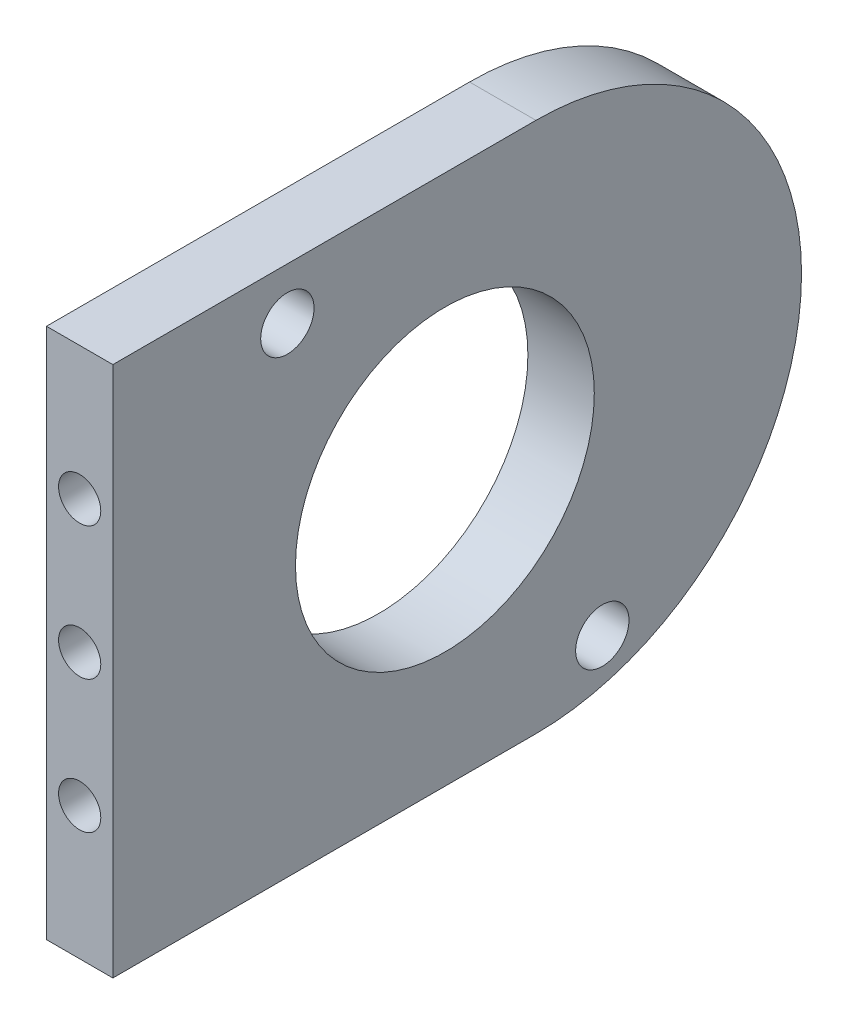
SolidWorks part; units mm, degrees
material "6061-T6 (SS)"
ref_plane "Front" through (0, 0, 0) normal (0, 0, 1) x (1, 0, 0)
ref_plane "Top" through (0, 0, 0) normal (0, 1, 0) x (1, 0, 0)
ref_plane "Right" through (0, 0, 0) normal (1, 0, 0) x (0, 0, -1)
sketch "Sketch2" plane through (0, 0, 0) normal (1, 0, 0) x (0, 0, -1)
  line L1 (-38.1, -25.4) -> (38.1, -25.4)
  line L2 (-38.1, -25.4) -> (-38.1, 25.4)
  line L3 (-38.1, 25.4) -> (38.1, 25.4)
  line L4 (38.1, -25.4) -> (38.1, 25.4)
  line L5 (-38.1, -25.4) -> (38.1, 25.4) construction
  line L6 (-38.1, 25.4) -> (38.1, -25.4) construction
  point P0 (0, 0)
  dimension "D1" = 76.2
  dimension "D2" = 50.8
extrude "Boss-Extrude2" add sketch "Sketch2" along normal blind 6.35
hole_wizard "#10-32 Tapped Hole1" positions "Sketch3" profile "Sketch5" tap size "#10-32" standard "ANSI Inch"
sketch "Sketch3" plane through (0, 0, 38.1) normal (0, 0, 1) x (1, 0, 0)
  line L0 (3.175, 25.4) -> (3.175, 12.7) construction
  line L1 (6.35, 25.4) -> (0, 25.4) construction
  line L3 (3.175, 12.7) -> (3.175, 0) construction
  line L4 (3.175, 0) -> (3.175, -12.7) construction
  line L5 (3.175, -12.7) -> (3.175, -25.4) construction
  line L6 (6.35, -25.4) -> (0, -25.4) construction
  point P0 (3.175, -12.7)
  point P2 (3.175, 0)
  point P6 (3.175, 12.7)
sketch "Sketch5" plane through (3.175, -12.7, 38.1) normal (1, 0, 0) x (0, -1, 0)
  line L0 (0, 0) -> (0, 13.2428)
  line L1 (0, 13.2428) -> (2.0193, 12.0294)
  line L2 (2.0193, 12.0294) -> (2.0193, 0)
  line L5 (2.0193, 0) -> (0, 0)
  line L10 (0, 13.2428) -> (-2.0193, 12.0294) construction
  line L11 (0, -6.35) -> (0, 107.95) construction
  dimension "Tap Drill Dia." = 4.0386
  dimension "Tap Drill Depth" = 12.0294
  dimension "Drill Angle" = 118
cosmetic thread "Hole Thread1" parameters "D1"=9.652, "D2"=4.826
cosmetic thread "Hole Thread3" parameters "D1"=9.652, "D2"=4.826
cosmetic thread "Hole Thread4" parameters "D1"=9.652, "D2"=4.826
sketch "Sketch6" plane through (6.35, 0, 0) normal (1, 0, 0) x (0, 0, -1)
  line L0 (-38.1, 25.4) -> (-38.1, -25.4) construction
  line L1 (-38.1, -25.4) -> (38.1, -25.4) construction
  circle A0 centre (-6.35, 0) radius 14.2875
  dimension "D1" = 31.75
  dimension "D3" = 28.575
  dimension "D2" = 25.4
extrude "Cut-Extrude1" cut sketch "Sketch6" against normal through all
sketch "Sketch10" plane through (0, 0, 0) normal (-1, 0, 0) x (0, 0, 1)
  point P3 (-8.7041, -20.4408)
  point P8 (21.4132, 20.4687)
hole_wizard "#10 Clearance Hole1" positions "Sketch10" profile "Sketch9" hole size "#10" standard "ANSI Inch"
sketch "Sketch9" plane through (0, -20.4408, -8.7041) normal (0, 1, 0) x (0, 0, 1)
  line L0 (0, 0) -> (0, 13.5633)
  line L1 (0, 13.5633) -> (2.5527, 12.0294)
  line L2 (2.5527, 12.0294) -> (2.5527, 0)
  line L5 (2.5527, 0) -> (0, 0)
  line L10 (0, 13.5633) -> (-2.5527, 12.0294) construction
  line L11 (0, -6.35) -> (0, 107.95) construction
  dimension "Hole Dia." = 5.1054
  dimension "Hole Depth" = 12.0294
  dimension "Drill Angle" = 118
sketch "Sketch13" plane through (6.35, 0, 0) normal (1, 0, 0) x (0, 0, -1)
  line L0 (27.7541, -25.4) -> (27.7541, 25.4)
  line L1 (-38.1, -25.4) -> (38.1, -25.4) construction
  line L2 (38.1, 25.4) -> (-38.1, 25.4) construction
  line L3 (27.7541, 25.4) -> (38.1, 25.4)
  line L4 (38.1, 25.4) -> (38.1, -25.4)
  line L5 (38.1, -25.4) -> (27.7541, -25.4)
  circle A0 centre (8.7041, -20.4408) radius 2.5527 construction
  dimension "D1" = 19.05
extrude "Cut-Extrude2" cut sketch "Sketch13" against normal through all
fillet "Fillet3" radius 25.4 2 edges at (3.175, 25.4, -27.7541) (3.175, -25.4, -27.7541)
